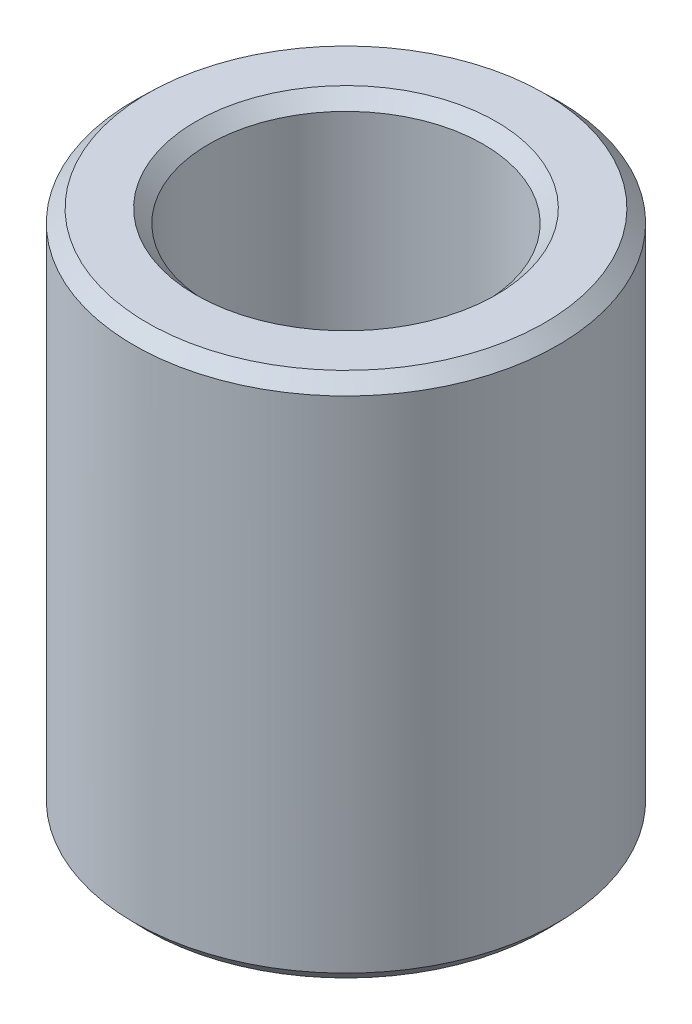
SolidWorks part; units mm, degrees
ref_plane "Front Plane" through (0, 0, 0) normal (0, 0, 1) x (1, 0, 0)
ref_plane "Top Plane" through (0, 0, 0) normal (0, 1, 0) x (1, 0, 0)
ref_plane "Right Plane" through (0, 0, 0) normal (1, 0, 0) x (0, 0, -1)
sketch "Sketch1" plane through (0, 0, 0) normal (0, 1, 0) x (1, 0, 0)
  circle A0 centre (0, 0) radius 22.5
  dimension "SLEEVE_OD" = 45
extrude "Boss-Extrude1" add sketch "Sketch1" along normal blind 55.8444
sketch "Sketch2" plane through (0, 0, 0) normal (0, 1, 0) x (1, 0, 0)
  circle A0 centre (0, 0) radius 14.5818
  dimension "BORE_D" = 29.1636
extrude "Cut-Extrude1" cut sketch "Sketch2" along normal through all
chamfer "Chamfer1" distance 1.3641 angle 45.884 4 edges at (0, 55.8444, 14.5818) (0, 0, 14.5818) (0, 0, 22.5) (0, 55.8444, 22.5) first distance on face at (0, 55.8444, 14.5818) first distance on face at (0, 0, 14.5818) first distance on face at (0, 55.8444, 22.5)
